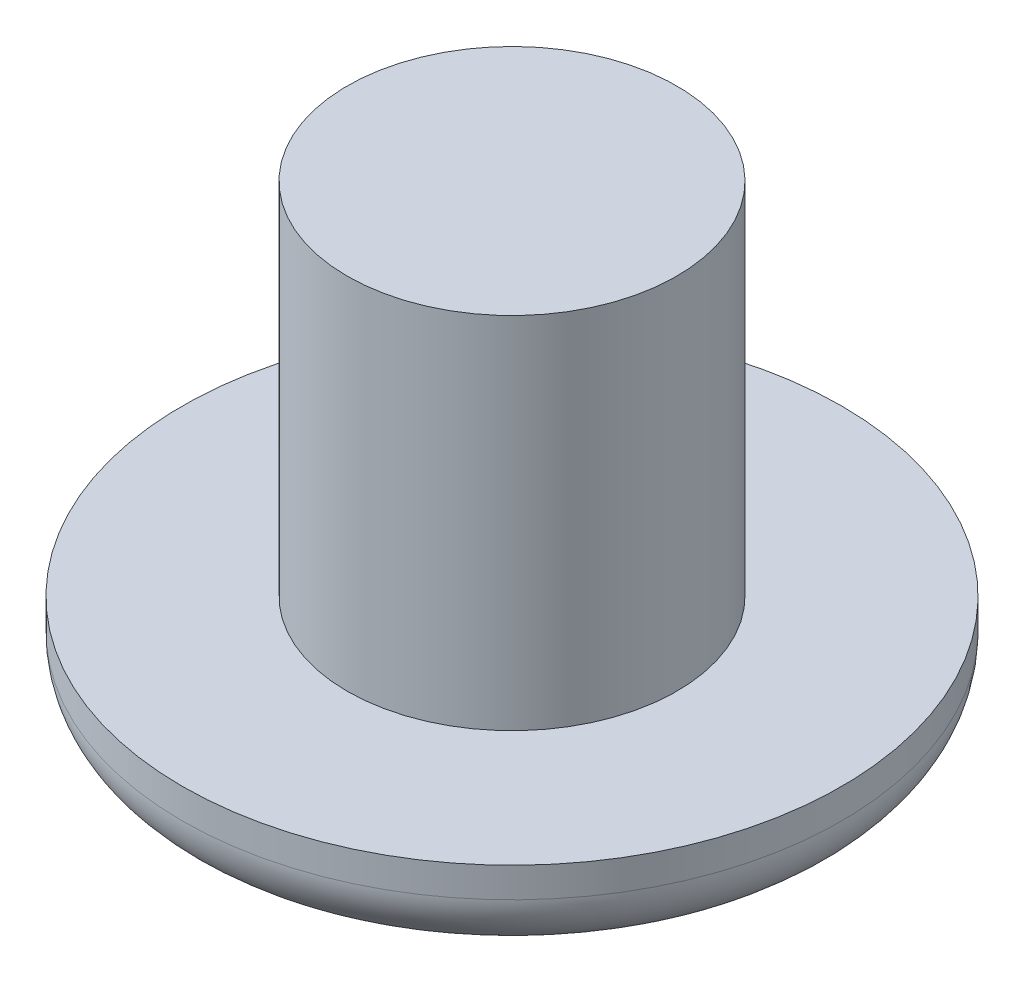
SolidWorks part; units mm, degrees
ref_plane "Front Plane" through (0, 0, 0) normal (0, 0, 1) x (1, 0, 0)
ref_plane "Top Plane" through (0, 0, 0) normal (0, 1, 0) x (1, 0, 0)
ref_plane "Right Plane" through (0, 0, 0) normal (1, 0, 0) x (0, 0, -1)
sketch "Sketch1" plane through (0, 0, 0) normal (0, 1, 0) x (1, 0, 0)
  circle A0 centre (0, 0) radius 5.5
  circle A1 centre (0, 0) radius 11
  dimension "D1" = 22
  dimension "D2" = 11
extrude "Boss-Extrude1" add sketch "Sketch1" along normal blind 12 contours A0 region at (0, 0, 0)
extrude "Boss-Extrude2" add sketch "Sketch1<3>" against normal blind 3 contours A1 A0 | A0 region at (-10.6889, 0, 0)
sketch "Sketch1<3>" plane through (0, 0, 0) normal (0, 1, 0) x (1, 0, 0) same geometry as "Sketch1"
fillet "Fillet1" radius 2 1 edges at (0, -3, 11)
